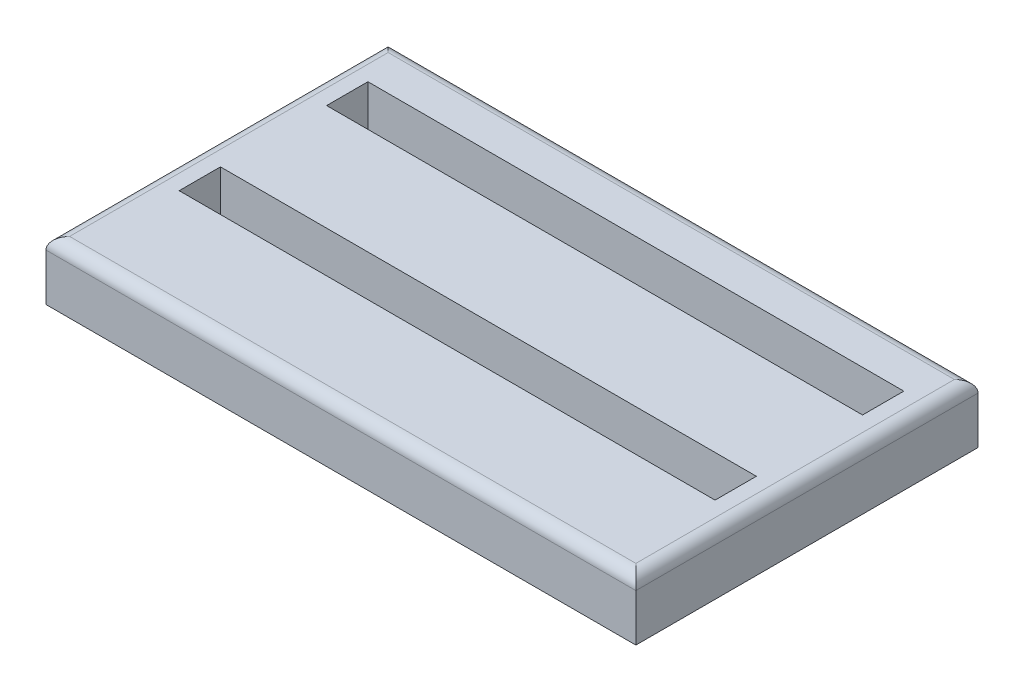
SolidWorks part; units mm, degrees
ref_plane "Front Plane" through (0, 0, 0) normal (0, 0, 1) x (1, 0, 0)
ref_plane "Top Plane" through (0, 0, 0) normal (0, 1, 0) x (1, 0, 0)
ref_plane "Right Plane" through (0, 0, 0) normal (1, 0, 0) x (0, 0, -1)
sketch "Sketch2" plane through (0, 0, 0) normal (0, 1, 0) x (1, 0, 0)
  line L0 (0, 242.4303) -> (0, -237.7501) construction
  line L1 (-63.5, 30.48) -> (-63.5, -43.18)
  line L2 (-63.5, 30.48) -> (63.5, 30.48)
  line L3 (-63.5, -43.18) -> (63.5, -43.18)
  line L4 (63.5, 30.48) -> (63.5, -43.18)
  dimension "D1" = 127
  dimension "D2" = 63.5
  dimension "D3" = 73.66
  dimension "D4" = 43.18
extrude "Boss-Extrude1" add sketch "Sketch2" along normal blind 12.7
fillet "Fillet1" radius 2.54 4 edges at (63.5, 12.7, 6.35) (-63.5, 12.7, 6.35) (0, 12.7, 43.18) (0, 12.7, -30.48)
sketch "Sketch3" plane through (0, 12.7, 0) normal (0, 1, 0) x (1, 0, 0)
  line L0 (57.6928, 11.43) -> (57.6928, 20.32)
  line L1 (57.6928, 11.43) -> (-57.6928, 11.43)
  line L2 (57.6928, 20.32) -> (-57.6928, 20.32)
  line L3 (-57.6928, 11.43) -> (-57.6928, 20.32)
  line L5 (63.5, 30.48) -> (63.5, -43.18) construction
  line L6 (-63.5, 30.48) -> (63.5, 30.48) construction
  line L7 (-60.96, -40.64) -> (60.96, -40.64) construction
  line L10 (57.6928, -11.43) -> (57.6928, -20.32)
  line L11 (57.6928, -20.32) -> (-57.6928, -20.32)
  line L12 (-57.6928, -11.43) -> (-57.6928, -20.32)
  line L13 (57.6928, -11.43) -> (-57.6928, -11.43)
  dimension "D1" = 115.3856
  dimension "D2" = 5.8072
  dimension "D3" = 10.16
  dimension "D4" = 8.89
  dimension "D5" = 20.32
extrude "Cut-Extrude1" cut sketch "Sketch3" against normal blind 12.7
